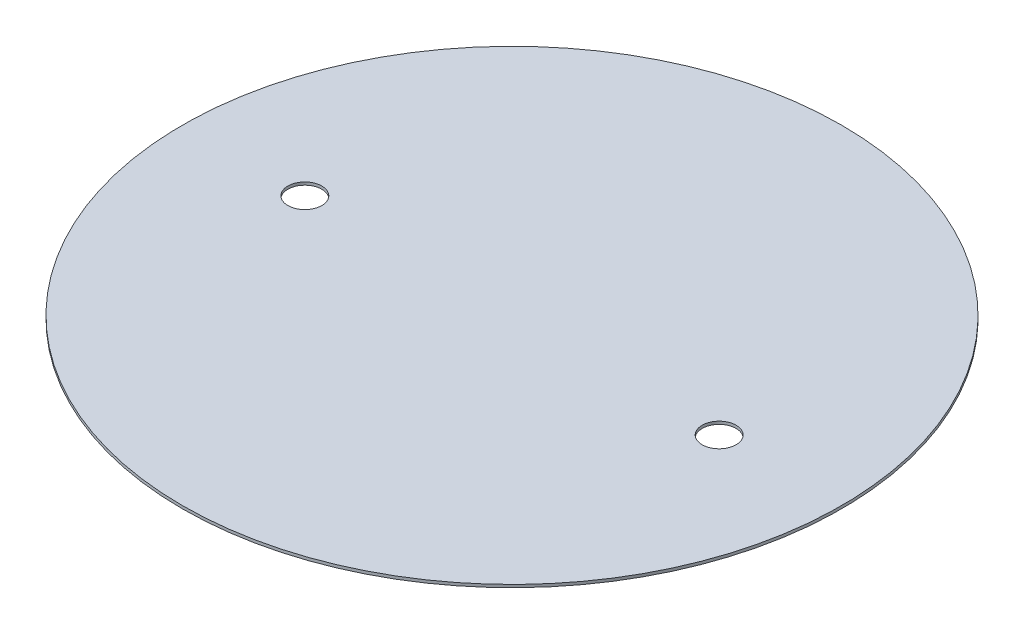
SolidWorks part; units mm, degrees
ref_plane "Front Plane" through (0, 0, 0) normal (0, 0, 1) x (1, 0, 0)
ref_plane "Top Plane" through (0, 0, 0) normal (0, 1, 0) x (1, 0, 0)
ref_plane "Right Plane" through (0, 0, 0) normal (1, 0, 0) x (0, 0, -1)
sketch "Sketch1" plane through (0, 0, 0) normal (0, 1, 0) x (1, 0, 0)
  circle A0 centre (0, 0) radius 1750
extrude "Boss-Extrude1" add sketch "Sketch1" along normal blind 15
sketch "Sketch2" plane through (0, 15, 0) normal (0, 1, 0) x (1, 0, 0)
  line L0 (-8.25, 0) -> (8.25, 0) construction
  line L1 (0, -8.25) -> (0, 8.25) construction
  circle A0 centre (-1100, 0) radius 90
  circle A1 centre (1100, 0) radius 90
extrude "Cut-Extrude1" cut sketch "Sketch2" against normal blind 50
